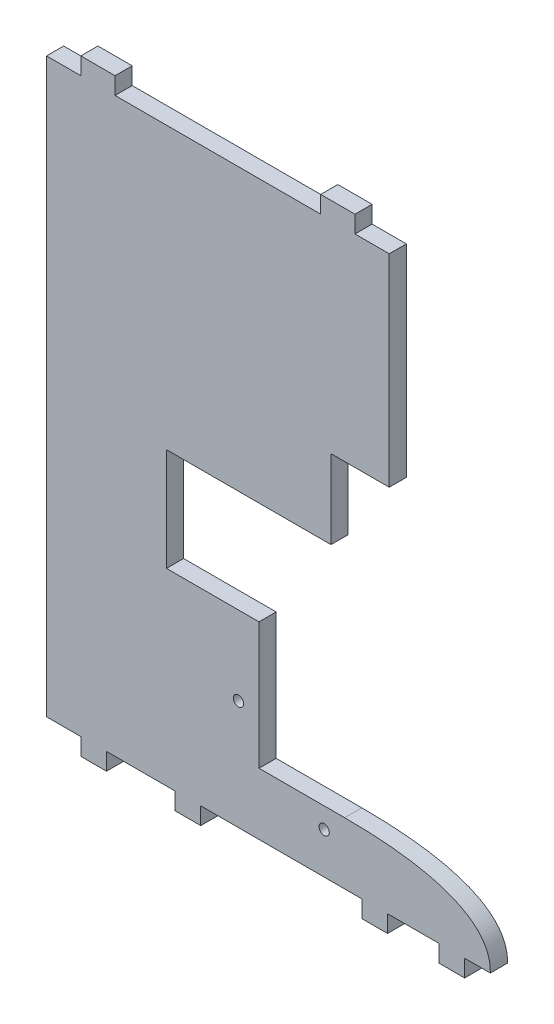
SolidWorks part; units mm, degrees
ref_plane "Plan de face" through (0, 0, 0) normal (0, 0, 1) x (1, 0, 0)
ref_plane "Plan de dessus" through (0, 0, 0) normal (0, 1, 0) x (1, 0, 0)
ref_plane "Plan de droite" through (0, 0, 0) normal (1, 0, 0) x (0, 0, -1)
sketch "Esquisse1" plane through (0, 0, 0) normal (0, 0, 1) x (1, 0, 0)
  line L1 (0, 0) -> (37, 0)
  line L2 (0, 0) -> (0, 55)
  line L3 (0, 55) -> (12, 55)
  line L4 (37, 0) -> (37, 18)
  line L6 (12, 55) -> (12, 18)
  line L7 (12, 18) -> (37, 18)
  circle A0 centre (6, 32) radius 1.5
  circle A1 centre (31, 12) radius 1.5
  dimension "D3" = 20
  dimension "D4" = 3
  dimension "D1" = 6
  dimension "D2" = 55
  dimension "D5" = 12
  dimension "D7" = 25
  dimension "D8" = 6
  dimension "D9" = 6
extrude "Boss.-Extru.1" add sketch "Esquisse1" along normal blind 5
sketch "Esquisse2" plane through (0, 0, 5) normal (0, 0, 1) x (1, 0, 0)
  line L0 (37, 18) -> (12, 18) construction
  line L1 (37, 0) -> (42, 0)
  line L2 (37, 0) -> (37, 18)
  line L3 (49.5, 0) -> (64.5, 0)
  line L4 (12, 55) -> (0, 55) construction
  line L5 (72, 0) -> (72, -5)
  line L6 (72, -5) -> (64.5, -5)
  line L7 (64.5, 0) -> (64.5, -5)
  line L8 (72, 0) -> (79.5, 0)
  line L9 (49.5, 0) -> (49.5, -5)
  line L10 (49.5, -5) -> (42, -5)
  line L11 (42, 0) -> (42, -5)
  line L12 (0, 0) -> (-5, 0)
  line L13 (0, 0) -> (0, 55)
  line L14 (0, 55) -> (-15, 55)
  line L15 (40, 167) -> (50, 167)
  line L16 (-12.5, 0) -> (-32.5, 0)
  line L17 (-40, 0) -> (-40, -5)
  line L18 (-15, 55) -> (-15, 85)
  line L19 (-40, -5) -> (-32.5, -5)
  line L20 (-50, 0) -> (-50, 167)
  line L21 (-50, 167) -> (-40, 167)
  line L22 (-32.5, 0) -> (-32.5, -5)
  line L23 (33, 85) -> (-15, 85)
  line L24 (50, 167) -> (50, 108)
  line L25 (-12.5, 0) -> (-12.5, -5)
  line L26 (-12.5, -5) -> (-5, -5)
  line L27 (-5, 0) -> (-5, -5)
  line L28 (-40, 0) -> (-50, 0)
  line L29 (-40, 167) -> (-40, 172)
  line L30 (-40, 172) -> (-30, 172)
  line L31 (-30, 167) -> (-30, 172)
  line L32 (-30, 167) -> (30, 167)
  line L33 (40, 167) -> (40, 172)
  line L34 (40, 172) -> (30, 172)
  line L35 (30, 167) -> (30, 172)
  line L38 (33, 85) -> (33, 108)
  line L39 (33, 108) -> (50, 108)
  spline S0 degree 3 poles (37, 18) (79.2395, 18) (79.5, 3.8743) (79.5, 0) knots 0 0 0 0 1 1 1 1
  dimension "D1" = 42.5
  dimension "D2" = 7.5
  dimension "D3" = 5
  dimension "D4" = 5
  dimension "D5" = 15
  dimension "D6" = 15
  dimension "D7" = 30
  dimension "D8" = 167
  dimension "D9" = 23
  dimension "D10" = 5
  dimension "D11" = 20
  dimension "D12" = 50
  dimension "D13" = 100
  dimension "D14" = 5
  dimension "D15" = 10
  dimension "D16" = 10
  dimension "D17" = 10
  dimension "D18" = 17
extrude "Boss.-Extru.2" add sketch "Esquisse2" against normal blind 5
